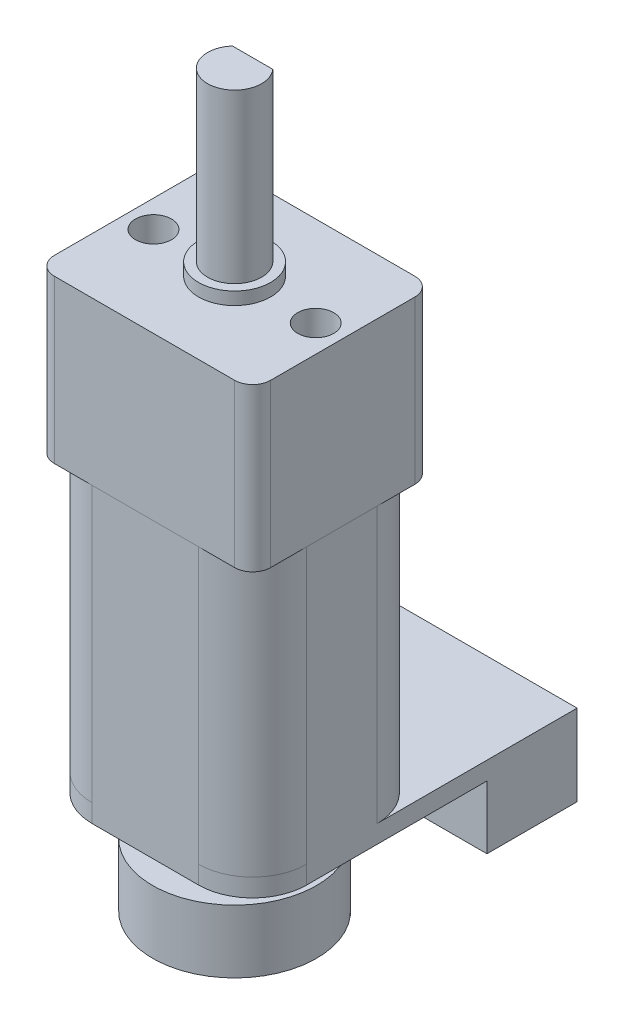
SolidWorks part; units mm, degrees
ref_plane "Front" through (0, 0, 0) normal (0, 0, 1) x (1, 0, 0)
ref_plane "Top" through (0, 0, 0) normal (0, 1, 0) x (1, 0, 0)
ref_plane "Right" through (0, 0, 0) normal (1, 0, 0) x (0, 0, -1)
sketch "草图1" plane through (0, 0, 0) normal (0, 1, 0) x (1, 0, 0)
  line L1 (6, -5) -> (-6, -5)
  line L2 (6, -5) -> (6, 5)
  line L3 (6, 5) -> (-6, 5)
  line L4 (-6, -5) -> (-6, 5)
  line L5 (6, -5) -> (-6, 5) construction
  line L6 (6, 5) -> (-6, -5) construction
  point P0 (0, 0)
  dimension "D1" = 12
  dimension "D2" = 10
extrude "凸台-拉伸1" add sketch "草图1" along normal blind 9
sketch "草图2" plane through (0, 9, 0) normal (0, 1, 0) x (1, 0, 0)
  line L0 (-18.2305, 0) -> (18.5757, 0) construction
  line L1 (0, 13.0159) -> (0, -8.9692) construction
  circle A0 centre (-4.5, 0) radius 1
  circle A1 centre (4.5, 0) radius 1
  dimension "D1" = 2
  dimension "D2" = 9
extrude "切除-拉伸1" cut sketch "草图2" against normal through all
sketch "草图3" plane through (0, 9, 0) normal (0, 1, 0) x (1, 0, 0)
  circle A0 centre (0, 0) radius 2
  dimension "D1" = 4
extrude "凸台-拉伸2" add sketch "草图3" along normal blind 0.7
sketch "草图4" plane through (0, 9.7, 0) normal (0, 1, 0) x (1, 0, 0)
  circle A0 centre (0, 0) radius 1.5
  dimension "D1" = 3
extrude "凸台-拉伸3" add sketch "草图4" along normal blind 9.3
sketch "草图5" plane through (0, 19, 0) normal (0, 1, 0) x (1, 0, 0)
  line L0 (0, 4.1191) -> (0, -4.2209) construction
  line L1 (-1.118, 1) -> (1.118, 1)
  arc A0 (-1.118, 1) -> (1.118, 1) centre (0, 0) ccw
  circle A1 centre (0, 0) radius 1.5 construction
  dimension "D1" = 1
extrude "切除-拉伸2" cut sketch "草图5" against normal blind 9.3 flip side to cut
fillet "圆角1" radius 1 4 edges at (-6, 4.5, 5) (6, 4.5, 5) (6, 4.5, -5) (-6, 4.5, -5)
ref_plane "基准面1" through (0, 0, 0) normal (0, -1, 0) x (-1, 0, 0)
sketch "草图6" plane through (0, 0, 0) normal (0, -1, 0) x (1, 0, 0)
  line L1 (5.95, -4.95) -> (-5.95, -4.95)
  line L2 (5.95, -4.95) -> (5.95, 4.95)
  line L3 (5.95, 4.95) -> (-5.95, 4.95)
  line L4 (-5.95, -4.95) -> (-5.95, 4.95)
  line L5 (5.95, -4.95) -> (-5.95, 4.95) construction
  line L6 (5.95, 4.95) -> (-5.95, -4.95) construction
  point P0 (0, 0)
  dimension "D1" = 11.9
  dimension "D2" = 9.9
extrude "凸台-拉伸4" add sketch "草图6" along normal blind 15.3
fillet "圆角3" radius 3 4 edges at (5.95, -7.65, 4.95) (5.95, -7.65, -4.95) (-5.95, -7.65, -4.95) (-5.95, -7.65, 4.95)
sketch "草图7" plane through (0, -15.3, 0) normal (0, -1, 0) x (1, 0, 0)
  line L0 (0, 11.7145) -> (0, -13.3938) construction
  line L6 (-5.95, 1.95) -> (-5.95, -1.95) construction
  line L7 (5.95, -13.05) -> (-5.95, -13.05)
  line L12 (5.95, -13.05) -> (5.95, 4.95)
  line L13 (5.95, 4.95) -> (-5.95, 4.95)
  line L14 (-5.95, -13.05) -> (-5.95, 4.95)
  line L15 (5.95, -13.05) -> (-5.95, 4.95) construction
  line L16 (5.95, 4.95) -> (-5.95, -13.05) construction
  line L17 (2.95, 4.95) -> (-2.95, 4.95) construction
  point P3 (0, -9)
  point P4 (0, -4.05)
  dimension "D1" = 18
extrude "凸台-拉伸5" add sketch "草图7" along normal blind 1
fillet "圆角4" radius 3 2 edges at (5.95, -15.8, 4.95) (-5.95, -15.8, 4.95)
sketch "草图8" plane through (0, -16.3, 0) normal (0, -1, 0) x (1, 0, 0)
  circle A0 centre (0, 0) radius 0.5
  dimension "D1" = 1
extrude "凸台-拉伸6" add sketch "草图8" along normal blind 5.2
sketch "草图9" plane through (0, -21.5, 0) normal (0, -1, 0) x (1, 0, 0)
  circle A1 centre (0, 0) radius 4.55
  dimension "D1" = 9.1
extrude "凸台-拉伸7" add sketch "草图9" against normal blind 3.5
sketch "草图10" plane through (0, -16.3, 0) normal (0, -1, 0) x (1, 0, 0)
  line L0 (0, -20.8502) -> (0, 11.1536) construction
  line L1 (-5.95, 1.95) -> (-5.95, -13.05) construction
  line L2 (5.95, -13.05) -> (-5.95, -13.05)
  line L3 (5.95, -13.05) -> (5.95, -8.05)
  line L4 (5.95, -8.05) -> (-5.95, -8.05)
  line L5 (-5.95, -13.05) -> (-5.95, -8.05)
  line L6 (5.95, -13.05) -> (-5.95, -8.05) construction
  line L7 (5.95, -8.05) -> (-5.95, -13.05) construction
  line L8 (-5.95, -13.05) -> (5.95, -13.05) construction
  point P3 (0, -10.55)
  dimension "D1" = 5
extrude "凸台-拉伸8" add sketch "草图10" along normal blind 3.5
sketch "草图11" plane through (0, 0, -13.05) normal (0, 0, -1) x (-1, 0, 0)
  line L0 (-5.95, -17.55) -> (11.8828, -17.55) construction
  line L1 (5.5, -19.55) -> (-5.5, -19.55)
  line L2 (5.5, -19.55) -> (5.5, -15.55)
  line L3 (5.5, -15.55) -> (-5.5, -15.55)
  line L4 (-5.5, -19.55) -> (-5.5, -15.55)
  line L5 (5.5, -19.55) -> (-5.5, -15.55) construction
  line L6 (5.5, -15.55) -> (-5.5, -19.55) construction
  line L7 (-5.95, -19.8) -> (-5.95, -15.3) construction
  point P0 (0, -17.55)
  dimension "D1" = 11
  dimension "D2" = 4
extrude "切除-拉伸3" cut sketch "草图11" against normal blind 3
